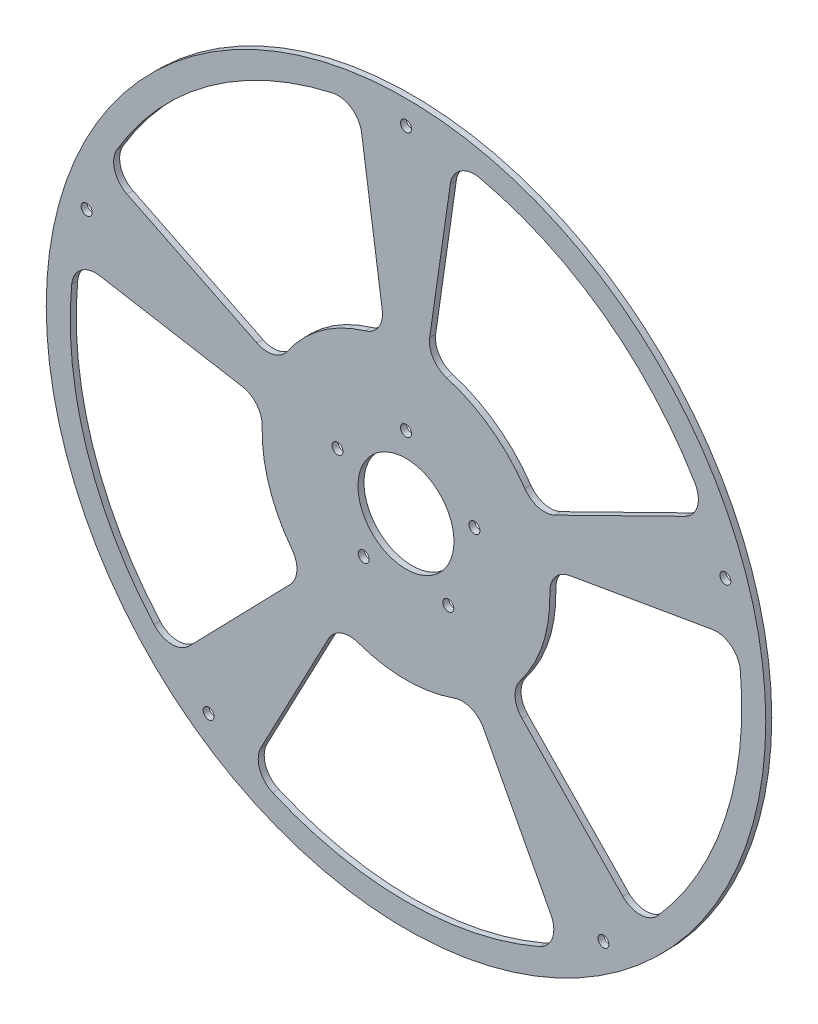
SolidWorks part; units mm, degrees
ref_plane "Front Plane" through (0, 0, 0) normal (0, 0, 1) x (1, 0, 0)
ref_plane "Top Plane" through (0, 0, 0) normal (0, 1, 0) x (1, 0, 0)
ref_plane "Right Plane" through (0, 0, 0) normal (1, 0, 0) x (0, 0, -1)
sketch "Sketch1" plane through (0, 0, 0) normal (0, 0, 1) x (1, 0, 0)
  line L0 (0, 177.8) -> (0, 0) construction
  line L1 (0, 0) -> (169.0978, 54.9432) construction
  line L2 (-169.0978, 54.9432) -> (0, 0) construction
  line L3 (0, 0) -> (-104.5082, -143.8432) construction
  line L4 (0, 0) -> (104.5082, -143.8432) construction
  line L5 (25.3351, 175.9857) -> (10.8579, 75.4224)
  line L6 (-25.4, 175.9764) -> (-10.8857, 75.4184)
  line L7 (68.3757, 33.6333) -> (159.5434, 78.4777)
  line L8 (75.0863, 12.9803) -> (175.2013, 30.2874)
  line L9 (53.1164, -54.6359) -> (123.9384, -127.4838)
  line L10 (35.548, -67.4002) -> (82.9453, -157.267)
  line L11 (-159.5434, 78.4777) -> (-68.3757, 33.6333)
  line L12 (-175.2013, 30.2874) -> (-75.0863, 12.9803)
  line L13 (-82.9453, -157.267) -> (-35.548, -67.4002)
  line L14 (-123.9384, -127.4838) -> (-53.1164, -54.6359)
  circle A0 centre (0, 0) radius 190.5
  arc A1 (-10.8857, 75.4184) -> (-68.3757, 33.6333) centre (0, 0) ccw
  arc A2 (-25.4, 175.9764) -> (-159.5434, 78.4777) centre (0, 0) ccw
  arc A3 (68.3757, 33.6333) -> (10.8579, 75.4224) centre (0, 0) ccw
  arc A4 (-75.0863, 12.9803) -> (-53.1164, -54.6359) centre (0, 0) ccw
  arc A5 (53.1164, -54.6359) -> (75.0863, 12.9803) centre (0, 0) ccw
  arc A6 (-35.548, -67.4002) -> (35.548, -67.4002) centre (0, 0) ccw
  arc A7 (159.5434, 78.4777) -> (25.3351, 175.9857) centre (0, 0) ccw
  arc A8 (123.9384, -127.4838) -> (175.2013, 30.2874) centre (0, 0) ccw
  arc A9 (-82.9453, -157.267) -> (82.9453, -157.267) centre (0, 0) ccw
  arc A10 (-175.2013, 30.2874) -> (-123.9384, -127.4838) centre (0, 0) ccw
  circle A11 centre (0, 0) radius 76.2 construction
  circle A12 centre (0, 0) radius 177.8 construction
  circle A13 centre (0, 0) radius 25.4
  circle A14 centre (-36.2353, 11.7735) radius 2.9
  circle A15 centre (-22.3946, -30.8235) radius 2.9
  circle A16 centre (22.3946, -30.8235) radius 2.9
  circle A17 centre (36.2353, 11.7735) radius 2.9
  circle A18 centre (0, 38.1) radius 2.9
  circle A19 centre (-169.0978, 54.9432) radius 2.9
  circle A20 centre (0, 177.8) radius 2.9
  circle A21 centre (169.0978, 54.9432) radius 2.9
  circle A22 centre (104.5082, -143.8432) radius 2.9
  circle A23 centre (-104.5082, -143.8432) radius 2.9
  point P55 (0, 0)
  dimension "D1" = 381
  dimension "D2" = 152.4
  dimension "D3" = 355.6
  dimension "D22" = 50.8
  dimension "D23" = 5.8
  dimension "D24" = 5.8
  dimension "D25" = 5.8
  dimension "D26" = 5.8
  dimension "D27" = 5.8
  dimension "D33" = 5.8
  dimension "D4" = 72
  dimension "D5" = 72
  dimension "D6" = 72
  dimension "D7" = 72
  dimension "D8" = 25.4
  dimension "D9" = 25.4
  dimension "D10" = 25.4
  dimension "D11" = 25.4
  dimension "D12" = 25.4
  dimension "D13" = 25.4
  dimension "D14" = 25.4
  dimension "D15" = 25.4
  dimension "D16" = 25.4
  dimension "D17" = 25.4
  dimension "D18" = 21.7158
  dimension "D19" = 50.6702
  dimension "D20" = 50.6702
  dimension "D21" = 50.7351
  dimension "D28" = 38.1
  dimension "D29" = 38.1
  dimension "D30" = 38.1
  dimension "D31" = 38.1
  dimension "D32" = 38.1
  dimension "D34" = 5
extrude "Boss-Extrude3" add sketch "Sketch1" along normal blind 3.175
fillet "Fillet1" radius 12.7 1 edges at (-175.2013, 30.2874, 1.5875)
fillet "Fillet2" radius 12.7 13 edges at (35.548, -67.4002, 1.5875) (123.9384, -127.4838, 1.5875) (53.1164, -54.6359, 1.5875) (75.0863, 12.9803, 1.5875) (175.2013, 30.2874, 1.5875) (68.3757, 33.6333, 1.5875) (159.5434, 78.4777, 1.5875) (25.3351, 175.9857, 1.5875) (10.8579, 75.4224, 1.5875) (-10.8857, 75.4184, 1.5875) (-68.3757, 33.6333, 1.5875) (-25.4, 175.9764, 1.5875) (-159.5434, 78.4777, 1.5875)
fillet "Fillet3" radius 12.7 6 edges at (-75.0863, 12.9803, 1.5875) (-123.9384, -127.4838, 1.5875) (-53.1164, -54.6359, 1.5875) (82.9453, -157.267, 1.5875) (-82.9453, -157.267, 1.5875) (-35.548, -67.4002, 1.5875)
